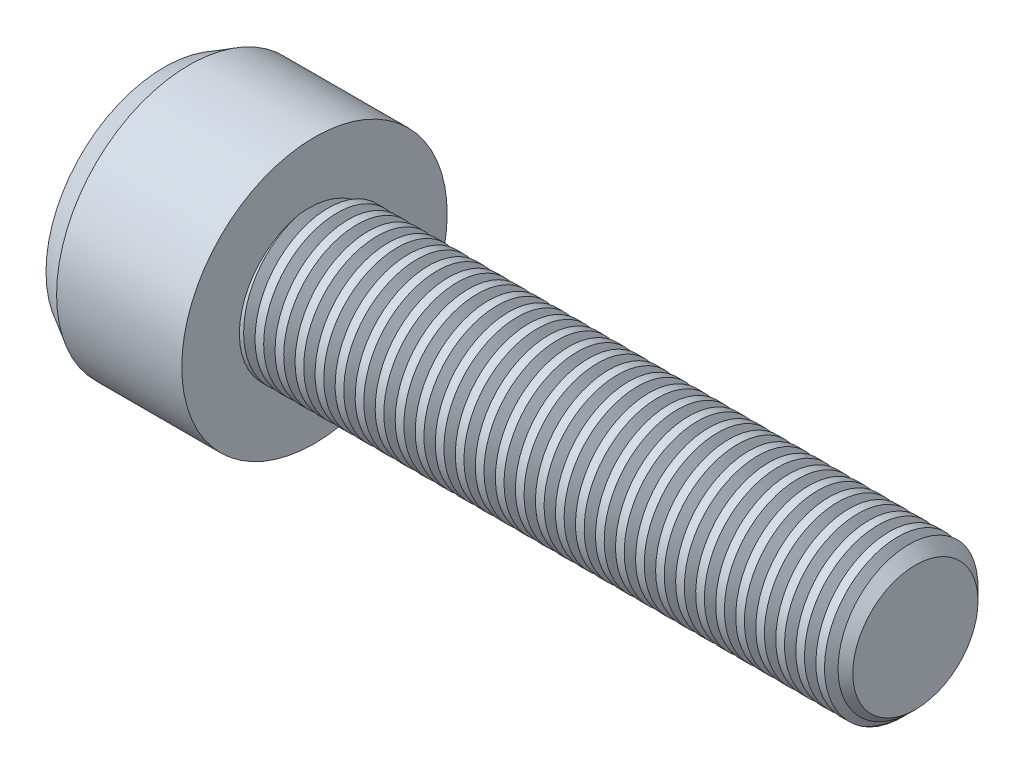
SolidWorks part; units mm, degrees
ref_plane "Front Plane" through (0, 0, 0) normal (0, 0, 1) x (1, 0, 0)
ref_plane "Top Plane" through (0, 0, 0) normal (0, 1, 0) x (1, 0, 0)
ref_plane "Right Plane" through (0, 0, 0) normal (1, 0, 0) x (0, 0, -1)
sketch "Sketch1" plane through (0, 0, 0) normal (1, 0, 0) x (0, 0, -1)
  circle A0 centre (0, 0) radius 2.65
  dimension "D1" = 5.3
extrude "Boss-Extrude4" add sketch "Sketch1" along normal blind 2.5
sketch "Sketch5" plane through (0, 0, 0) normal (-1, 0, 0) x (0, 0, 1)
  circle A0 centre (0, 0) radius 2.65
  circle A1 centre (0, 0) radius 2.65 construction
  dimension "D1" = 5.3
extrude "Boss-Extrude5" add sketch "Sketch5" along normal blind 0.5 draft 30
sketch "Sketch6" plane through (-0.5, 0, 0) normal (-1, 0, 0) x (0, 0, 1)
  line L1 (1.5011, 0) -> (0.7506, 1.3)
  line L2 (0.7506, 1.3) -> (-0.7506, 1.3)
  line L3 (-0.7506, 1.3) -> (-1.5011, 0)
  line L4 (-1.5011, 0) -> (-0.7506, -1.3)
  line L5 (-0.7506, -1.3) -> (0.7506, -1.3)
  line L6 (0.7506, -1.3) -> (1.5011, 0)
  circle A0 centre (0, 0) radius 1.3 construction
  circle A1 centre (0, 0) radius 2.3613 construction
  dimension "D1" = 2.6
extrude "Cut-Extrude5" cut sketch "Sketch6" against normal blind 1.5
sketch "Sketch7" plane through (1, 0, 0) normal (-1, 0, 0) x (0, 0, 1)
  line L0 (1.5011, 0) -> (0.7506, 1.3) construction
  line L1 (0.7506, 1.3) -> (-0.7506, 1.3)
  line L2 (-0.7506, 1.3) -> (-1.5011, 0)
  line L3 (-1.5011, 0) -> (-0.7506, -1.3)
  line L4 (-0.7506, -1.3) -> (0.7506, -1.3)
  line L5 (0.7506, -1.3) -> (1.5011, 0)
  line L6 (1.5011, 0) -> (0.7506, 1.3)
  line L7 (0.7506, 1.3) -> (-0.7506, 1.3) construction
  line L8 (0.7506, -1.3) -> (1.5011, 0) construction
  circle A0 centre (0, 0) radius 1.3 construction
extrude "Cut-Extrude11" cut sketch "Sketch7" against normal blind 0.25 draft 80
sketch "Sketch8" plane through (2.5, 0, 0) normal (1, 0, 0) x (0, 0, -1)
  circle A0 centre (0, 0) radius 1.5
  circle A1 centre (0, 0) radius 2.65 construction
  dimension "D1" = 3
extrude "Boss-Extrude8" add sketch "Sketch8" along normal blind 12
chamfer "Chamfer5" distance 0.25 angle 45 1 edges at (14.5, 0, -1.5)
sketch "Sketch12" plane through (14.5, 0, 0) normal (1, 0, 0) x (0, 0, -1)
  circle A0 centre (0, 0) radius 1.5
  circle A1 centre (0, 0) radius 1.25 construction
  dimension "D1" = 3
curve "Helix/Spiral1" pitch 0.4 height 12 radius 1.5 centre (14.5, 0, 0) axis (-1, 0, 0) start towards (0, 0, -1)
sketch "Sketch13" plane through (0, 0, 0) normal (0, 1, 0) x (1, 0, 0)
  line L1 (14.5, 1.3037) -> (14.67, 1.5981)
  line L2 (14.67, 1.5981) -> (14.33, 1.5981)
  line L3 (14.33, 1.5981) -> (14.5, 1.3037)
  dimension "D1" = 14.33
  dimension "D2" = 14.5
  dimension "D3" = 1.3037
sweep "Cut-Sweep1" cut profiles "Sketch13" path "Helix/Spiral1" align with end faces yes
